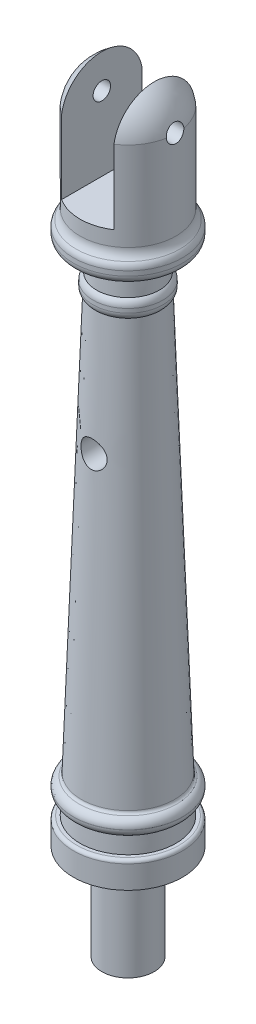
SolidWorks part; units mm, degrees
ref_plane "Front Plane" through (0, 0, 0) normal (0, 0, 1) x (1, 0, 0)
ref_plane "Top Plane" through (0, 0, 0) normal (0, 1, 0) x (1, 0, 0)
ref_plane "Right Plane" through (0, 0, 0) normal (1, 0, 0) x (0, 0, -1)
sketch "Sketch1" plane through (0, 0, 0) normal (0, 0, 1) x (1, 0, 0)
  line L0 (0, 0) -> (0, 114)
  line L1 (0, 114) -> (7, 114)
  line L2 (7, 114) -> (11, 0)
  line L3 (11, 0) -> (0, 0)
  dimension "D1" = 114
  dimension "D2" = 7
  dimension "D3" = 11
revolve "Revolve1" add sketch "Sketch1" angle 360 about L0
sketch "Sketch2" plane through (0, 0, 0) normal (0, -1, 0) x (1, 0, 0)
  circle A0 centre (0, 0) radius 12.5
  dimension "D1" = 25
extrude "Boss-Extrude1" add sketch "Sketch2" along normal blind 6
sketch "Sketch3" plane through (0, -6, 0) normal (0, -1, 0) x (1, 0, 0)
  circle A1 centre (0, 0) radius 12.5
  circle A2 centre (0, 0) radius 12.5
  dimension "D1" = 0
extrude "Boss-Extrude2" add sketch "Sketch3" along normal mid plane 4 from offset 12 offset against normal yes
fillet "Fillet1" radius 2 2 edges at (0, 8, -12.5) (0, 4, -12.5)
fillet "Fillet2" radius 0.75 1 edges at (0, 0, -12.5)
sketch "Sketch4" plane through (0, -6, 0) normal (0, -1, 0) x (1, 0, 0)
  circle A0 centre (0, 0) radius 6
  dimension "D1" = 12
extrude "Boss-Extrude3" add sketch "Sketch4" along normal blind 22
sketch "Sketch5" plane through (0, -28, 0) normal (0, -1, 0) x (1, 0, 0)
  line L0 (-5, 3.3166) -> (-5, -3.3166)
  circle A1 centre (0, 0) radius 6
  arc A2 (-5, 3.3166) -> (-5, -3.3166) centre (0, 0) ccw
  dimension "D2" = 5
  dimension "D1" = 0
extrude "Cut-Extrude1" cut sketch "Sketch5" against normal blind 15
sketch "Sketch6" plane through (0, 114, 0) normal (0, 1, 0) x (1, 0, 0)
  circle A0 centre (0, 0) radius 8
  dimension "D1" = 16
extrude "Boss-Extrude4" add sketch "Sketch6" along normal mid plane 4 from offset 8 offset against normal yes
fillet "Fillet3" radius 2 2 edges at (0, 104, 8) (0, 108, 8)
sketch "Sketch7" plane through (0, 114, 0) normal (0, 1, 0) x (1, 0, 0)
  circle A0 centre (0, 0) radius 12.5
  dimension "D1" = 25
extrude "Boss-Extrude5" add sketch "Sketch7" along normal blind 5
sketch "Sketch8" plane through (0, 119, 0) normal (0, 1, 0) x (1, 0, 0)
  circle A0 centre (0, 0) radius 11
  dimension "D1" = 22
extrude "Boss-Extrude6" add sketch "Sketch8" along normal blind 22
fillet "Fillet4" radius 2 2 edges at (0, 114, 12.5) (0, 119, 12.5)
fillet "Fillet5" radius 3 1 edges at (0, 119, 11)
fillet "Fillet6" radius 0.75 1 edges at (0, 8, -10.7193)
sketch "Sketch9" plane through (0, 0, 0) normal (0, 0, 1) x (1, 0, 0)
  line L0 (0, 150.5) -> (0, 141)
  line L1 (11, 141) -> (-11, 141) construction
  line L2 (0, 141) -> (11, 141)
  arc A0 (0, 150.5) -> (11, 141) centre (0.1027, 139.5005) cw
  dimension "D2" = 11
  dimension "D1" = 9.5
revolve "Revolve2" add sketch "Sketch9" angle 360 about L0
sketch "Sketch10" plane through (0, 0, 0) normal (0, 0, 1) x (1, 0, 0)
  line L0 (0, 120.6342) -> (0, 155.2264) construction
  line L1 (11, 120.6342) -> (-11, 120.6342) construction
  line L2 (11, 141) -> (-11, 141) construction
  line L3 (-6, 152) -> (6, 152)
  line L4 (-6, 152) -> (-6, 124)
  line L5 (-6, 124) -> (6, 124)
  line L6 (6, 152) -> (6, 124)
  dimension "D1" = 17
  dimension "D2" = 12
  dimension "D3" = 28
extrude "Cut-Extrude2" cut sketch "Sketch10" against normal through all both and the other way through all
sketch "Sketch11" plane through (0, 0, 0) normal (0, 0, 1) x (1, 0, 0)
  line L0 (-12.5, -6) -> (12.5, -6) construction
  circle A0 centre (0, 76) radius 3
  dimension "D1" = 82
  dimension "D2" = 6
extrude "Cut-Extrude3" cut sketch "Sketch11" against normal through all both and the other way through all
sketch "Sketch12" plane through (0, 0, 0) normal (1, 0, 0) x (0, 0, -1)
  line L0 (-9.2195, 141) -> (9.2195, 141) construction
  circle A0 centre (0, 141) radius 2
  dimension "D1" = 4
extrude "Cut-Extrude4" cut sketch "Sketch12" against normal through all both and the other way through all
